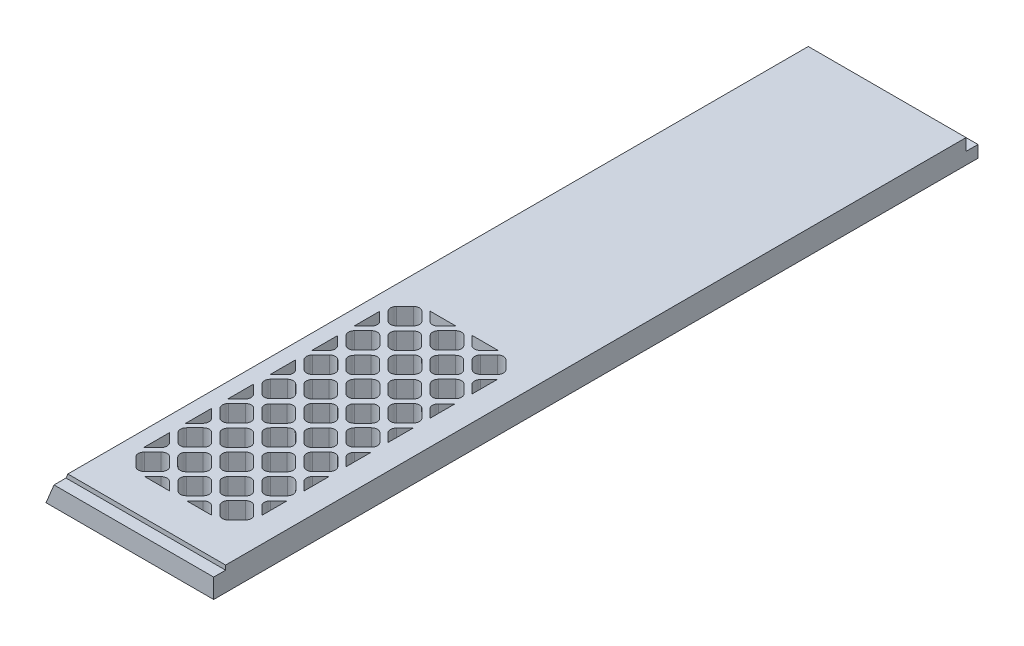
SolidWorks part; units mm, degrees
ref_plane "Front Plane" through (0, 0, 0) normal (0, 0, 1) x (1, 0, 0)
ref_plane "Top Plane" through (0, 0, 0) normal (0, 1, 0) x (1, 0, 0)
ref_plane "Right Plane" through (0, 0, 0) normal (1, 0, 0) x (0, 0, -1)
sketch "Sketch1" plane through (0, 0, 0) normal (0, 0, 1) x (1, 0, 0)
  line L0 (0, 0) -> (5.2605, 12.7)
  line L1 (5.2605, 12.7) -> (89.154, 12.7)
  line L2 (89.154, 12.7) -> (89.154, 0)
  line L3 (89.154, 0) -> (0, 0)
  dimension "D1" = 12.7
  dimension "D2" = 89.154
  dimension "D3" = 67.5
extrude "Boss-Extrude1" add sketch "Sketch1" along normal blind 406.4
sketch "Sketch2" plane through (0, 12.7, 0) normal (0, -1, 0) x (1, 0, 0)
  line L5 (89.154, 406.4) -> (89.154, 0) construction
  line L6 (0, 406.4) -> (89.154, 406.4)
  line L7 (0, 406.4) -> (0, 400.05)
  line L8 (0, 400.05) -> (89.154, 400.05)
  line L9 (89.154, 406.4) -> (89.154, 400.05)
  dimension "D2" = 6.35
extrude "Cut-Extrude1" cut sketch "Sketch2" along normal blind 2.3622
sketch "Sketch3" plane through (0, 0, 0) normal (0, -1, 0) x (1, 0, 0)
  line L90 (0, 203.2) -> (89.154, 203.2) construction
  line L91 (0, 406.4) -> (0, 0) construction
  line L221 (89.154, 406.4) -> (89.154, 0) construction
  line L222 (13.3842, 233.4919) -> (17.8743, 229.0018)
  line L223 (17.8743, 246.8637) -> (13.3842, 242.3736)
  line L235 (13.3842, 255.8439) -> (17.8743, 251.3538)
  line L236 (17.8743, 269.2157) -> (13.3842, 264.7256)
  line L237 (13.3842, 278.1959) -> (17.8743, 273.7058)
  line L238 (17.8743, 291.5677) -> (13.3842, 287.0776)
  line L239 (13.3842, 300.5479) -> (17.8743, 296.0578)
  line L240 (17.8743, 313.9197) -> (13.3842, 309.4296)
  line L241 (13.3842, 322.8999) -> (17.8743, 318.4098)
  line L242 (17.8743, 336.2717) -> (13.3842, 331.7816)
  line L243 (13.3842, 345.2519) -> (17.8743, 340.7618)
  line L244 (17.8743, 358.6237) -> (13.3842, 354.1336)
  line L245 (13.3842, 367.6039) -> (17.8743, 363.1138)
  line L246 (71.4599, 229.0018) -> (75.9093, 233.4512)
  line L247 (49.1079, 229.0018) -> (53.598, 233.4919)
  line L248 (58.0882, 233.4919) -> (62.5783, 229.0018)
  line L249 (26.7559, 229.0018) -> (31.246, 233.4919)
  line L250 (35.7362, 233.4919) -> (40.2263, 229.0018)
  line L251 (71.4599, 251.3538) -> (75.9093, 255.8032)
  line L252 (75.9093, 242.4143) -> (71.4599, 246.8637)
  line L253 (49.1079, 251.3538) -> (53.598, 255.8439)
  line L254 (53.598, 242.3736) -> (49.1079, 246.8637)
  line L255 (62.5783, 246.8637) -> (58.0882, 242.3736)
  line L256 (58.0882, 255.8439) -> (62.5783, 251.3538)
  line L257 (26.7559, 251.3538) -> (31.246, 255.8439)
  line L258 (31.246, 242.3736) -> (26.7559, 246.8637)
  line L259 (40.2263, 246.8637) -> (35.7362, 242.3736)
  line L260 (35.7362, 255.8439) -> (40.2263, 251.3538)
  line L261 (71.4599, 273.7058) -> (75.9093, 278.1552)
  line L262 (75.9093, 264.7663) -> (71.4599, 269.2157)
  line L263 (49.1079, 273.7058) -> (53.598, 278.1959)
  line L264 (53.598, 264.7256) -> (49.1079, 269.2157)
  line L265 (62.5783, 269.2157) -> (58.0882, 264.7256)
  line L266 (58.0882, 278.1959) -> (62.5783, 273.7058)
  line L267 (26.7559, 273.7058) -> (31.246, 278.1959)
  line L268 (31.246, 264.7256) -> (26.7559, 269.2157)
  line L269 (40.2263, 269.2157) -> (35.7362, 264.7256)
  line L270 (35.7362, 278.1959) -> (40.2263, 273.7058)
  line L271 (71.4599, 296.0578) -> (75.9093, 300.5072)
  line L272 (75.9093, 287.1183) -> (71.4599, 291.5677)
  line L273 (49.1079, 296.0578) -> (53.598, 300.5479)
  line L274 (53.598, 287.0776) -> (49.1079, 291.5677)
  line L275 (62.5783, 291.5677) -> (58.0882, 287.0776)
  line L276 (58.0882, 300.5479) -> (62.5783, 296.0578)
  line L277 (26.7559, 296.0578) -> (31.246, 300.5479)
  line L278 (31.246, 287.0776) -> (26.7559, 291.5677)
  line L279 (40.2263, 291.5677) -> (35.7362, 287.0776)
  line L280 (35.7362, 300.5479) -> (40.2263, 296.0578)
  line L281 (71.4599, 318.4098) -> (75.9093, 322.8592)
  line L282 (75.9093, 309.4703) -> (71.4599, 313.9197)
  line L283 (49.1079, 318.4098) -> (53.598, 322.8999)
  line L284 (53.598, 309.4296) -> (49.1079, 313.9197)
  line L285 (62.5783, 313.9197) -> (58.0882, 309.4296)
  line L286 (58.0882, 322.8999) -> (62.5783, 318.4098)
  line L287 (26.7559, 318.4098) -> (31.246, 322.8999)
  line L288 (31.246, 309.4296) -> (26.7559, 313.9197)
  line L289 (40.2263, 313.9197) -> (35.7362, 309.4296)
  line L290 (35.7362, 322.8999) -> (40.2263, 318.4098)
  line L291 (71.4599, 340.7618) -> (75.9093, 345.2112)
  line L292 (75.9093, 331.8223) -> (71.4599, 336.2717)
  line L293 (49.1079, 340.7618) -> (53.598, 345.2519)
  line L294 (53.598, 331.7816) -> (49.1079, 336.2717)
  line L295 (62.5783, 336.2717) -> (58.0882, 331.7816)
  line L296 (58.0882, 345.2519) -> (62.5783, 340.7618)
  line L297 (26.7559, 340.7618) -> (31.246, 345.2519)
  line L298 (31.246, 331.7816) -> (26.7559, 336.2717)
  line L299 (40.2263, 336.2717) -> (35.7362, 331.7816)
  line L300 (35.7362, 345.2519) -> (40.2263, 340.7618)
  line L301 (71.4599, 363.1138) -> (75.9093, 367.5632)
  line L302 (75.9093, 354.1743) -> (71.4599, 358.6237)
  line L303 (49.1079, 363.1138) -> (53.598, 367.6039)
  line L304 (53.598, 354.1336) -> (49.1079, 358.6237)
  line L305 (62.5783, 358.6237) -> (58.0882, 354.1336)
  line L306 (58.0882, 367.6039) -> (62.5783, 363.1138)
  line L307 (26.7559, 363.1138) -> (31.246, 367.6039)
  line L308 (31.246, 354.1336) -> (26.7559, 358.6237)
  line L309 (40.2263, 358.6237) -> (35.7362, 354.1336)
  line L310 (35.7362, 367.6039) -> (40.2263, 363.1138)
  line L311 (75.9093, 376.5263) -> (71.5993, 380.8363)
  line L312 (53.598, 376.4856) -> (49.2473, 380.8363)
  line L313 (62.4389, 380.8363) -> (58.0882, 376.4856)
  line L314 (31.246, 376.4856) -> (26.8953, 380.8363)
  line L315 (40.0869, 380.8363) -> (35.7362, 376.4856)
  line L316 (17.7349, 380.8363) -> (13.3842, 376.4856)
  line L317 (73.6642, 235.4989) -> (69.1741, 231.0088)
  line L318 (69.1741, 244.4792) -> (73.6642, 239.9891)
  line L319 (60.1938, 239.9891) -> (64.6839, 244.4792)
  line L320 (64.6839, 231.0088) -> (60.1938, 235.4989)
  line L321 (51.3122, 235.4989) -> (46.8221, 231.0088)
  line L322 (46.8221, 244.4792) -> (51.3122, 239.9891)
  line L323 (37.8418, 239.9891) -> (42.3319, 244.4792)
  line L324 (42.3319, 231.0088) -> (37.8418, 235.4989)
  line L325 (28.9602, 235.4989) -> (24.4701, 231.0088)
  line L326 (24.4701, 244.4792) -> (28.9602, 239.9891)
  line L327 (15.4898, 239.9891) -> (19.9799, 244.4792)
  line L328 (19.9799, 231.0088) -> (15.4898, 235.4989)
  line L329 (73.6642, 257.8509) -> (69.1741, 253.3608)
  line L330 (69.1741, 266.8312) -> (73.6642, 262.3411)
  line L331 (60.1938, 262.3411) -> (64.6839, 266.8312)
  line L332 (64.6839, 253.3608) -> (60.1938, 257.8509)
  line L333 (51.3122, 257.8509) -> (46.8221, 253.3608)
  line L334 (46.8221, 266.8312) -> (51.3122, 262.3411)
  line L335 (37.8418, 262.3411) -> (42.3319, 266.8312)
  line L336 (42.3319, 253.3608) -> (37.8418, 257.8509)
  line L337 (28.9602, 257.8509) -> (24.4701, 253.3608)
  line L338 (24.4701, 266.8312) -> (28.9602, 262.3411)
  line L339 (15.4898, 262.3411) -> (19.9799, 266.8312)
  line L340 (19.9799, 253.3608) -> (15.4898, 257.8509)
  line L341 (73.6642, 280.2029) -> (69.1741, 275.7128)
  line L342 (69.1741, 289.1832) -> (73.6642, 284.6931)
  line L343 (60.1938, 284.6931) -> (64.6839, 289.1832)
  line L344 (64.6839, 275.7128) -> (60.1938, 280.2029)
  line L345 (51.3122, 280.2029) -> (46.8221, 275.7128)
  line L346 (46.8221, 289.1832) -> (51.3122, 284.6931)
  line L347 (37.8418, 284.6931) -> (42.3319, 289.1832)
  line L348 (42.3319, 275.7128) -> (37.8418, 280.2029)
  line L349 (28.9602, 280.2029) -> (24.4701, 275.7128)
  line L350 (24.4701, 289.1832) -> (28.9602, 284.6931)
  line L351 (15.4898, 284.6931) -> (19.9799, 289.1832)
  line L352 (19.9799, 275.7128) -> (15.4898, 280.2029)
  line L353 (73.6642, 302.5549) -> (69.1741, 298.0648)
  line L354 (69.1741, 311.5352) -> (73.6642, 307.0451)
  line L355 (60.1938, 307.0451) -> (64.6839, 311.5352)
  line L356 (64.6839, 298.0648) -> (60.1938, 302.5549)
  line L357 (51.3122, 302.5549) -> (46.8221, 298.0648)
  line L358 (46.8221, 311.5352) -> (51.3122, 307.0451)
  line L359 (37.8418, 307.0451) -> (42.3319, 311.5352)
  line L360 (42.3319, 298.0648) -> (37.8418, 302.5549)
  line L361 (28.9602, 302.5549) -> (24.4701, 298.0648)
  line L362 (24.4701, 311.5352) -> (28.9602, 307.0451)
  line L363 (15.4898, 307.0451) -> (19.9799, 311.5352)
  line L364 (19.9799, 298.0648) -> (15.4898, 302.5549)
  line L365 (73.6642, 324.9069) -> (69.1741, 320.4168)
  line L366 (69.1741, 333.8872) -> (73.6642, 329.3971)
  line L367 (60.1938, 329.3971) -> (64.6839, 333.8872)
  line L368 (64.6839, 320.4168) -> (60.1938, 324.9069)
  line L369 (51.3122, 324.9069) -> (46.8221, 320.4168)
  line L370 (46.8221, 333.8872) -> (51.3122, 329.3971)
  line L371 (37.8418, 329.3971) -> (42.3319, 333.8872)
  line L372 (42.3319, 320.4168) -> (37.8418, 324.9069)
  line L373 (28.9602, 324.9069) -> (24.4701, 320.4168)
  line L374 (24.4701, 333.8872) -> (28.9602, 329.3971)
  line L375 (15.4898, 329.3971) -> (19.9799, 333.8872)
  line L376 (19.9799, 320.4168) -> (15.4898, 324.9069)
  line L377 (73.6642, 347.2589) -> (69.1741, 342.7688)
  line L378 (69.1741, 356.2392) -> (73.6642, 351.7491)
  line L379 (60.1938, 351.7491) -> (64.6839, 356.2392)
  line L380 (64.6839, 342.7688) -> (60.1938, 347.2589)
  line L381 (51.3122, 347.2589) -> (46.8221, 342.7688)
  line L382 (46.8221, 356.2392) -> (51.3122, 351.7491)
  line L383 (37.8418, 351.7491) -> (42.3319, 356.2392)
  line L384 (42.3319, 342.7688) -> (37.8418, 347.2589)
  line L385 (28.9602, 347.2589) -> (24.4701, 342.7688)
  line L386 (24.4701, 356.2392) -> (28.9602, 351.7491)
  line L387 (15.4898, 351.7491) -> (19.9799, 356.2392)
  line L388 (19.9799, 342.7688) -> (15.4898, 347.2589)
  line L389 (73.6642, 369.6109) -> (69.1741, 365.1208)
  line L390 (69.1741, 378.5912) -> (73.6642, 374.1011)
  line L391 (60.1938, 374.1011) -> (64.6839, 378.5912)
  line L392 (64.6839, 365.1208) -> (60.1938, 369.6109)
  line L393 (51.3122, 369.6109) -> (46.8221, 365.1208)
  line L394 (46.8221, 378.5912) -> (51.3122, 374.1011)
  line L395 (37.8418, 374.1011) -> (42.3319, 378.5912)
  line L396 (42.3319, 365.1208) -> (37.8418, 369.6109)
  line L397 (19.9799, 365.1208) -> (15.4898, 369.6109)
  line L398 (28.9602, 369.6109) -> (24.4701, 365.1208)
  line L399 (24.4701, 378.5912) -> (28.9602, 374.1011)
  line L400 (75.9093, 380.8363) -> (75.9093, 228.7637)
  line L401 (13.2447, 228.7637) -> (75.9093, 228.7637)
  line L402 (13.2447, 380.8363) -> (13.2447, 228.7637)
  line L403 (13.2447, 380.8363) -> (75.9093, 380.8363)
  line L404 (15.4898, 374.1011) -> (19.9799, 378.5912)
  arc A212 (18.0894, 228.7637) -> (17.8743, 229.0018) centre (15.6292, 226.7568) ccw
  arc A224 (13.2447, 233.6232) -> (13.3842, 233.4919) centre (11.1391, 231.2469) cw
  arc A225 (13.3842, 242.3736) -> (13.2447, 242.2423) centre (11.1391, 244.6186) cw
  arc A226 (17.8743, 246.8637) -> (17.8743, 251.3538) centre (15.6292, 249.1088) ccw
  arc A227 (13.2447, 255.9752) -> (13.3842, 255.8439) centre (11.1391, 253.5989) cw
  arc A228 (13.3842, 264.7256) -> (13.2447, 264.5943) centre (11.1391, 266.9706) cw
  arc A229 (17.8743, 269.2157) -> (17.8743, 273.7058) centre (15.6292, 271.4608) ccw
  arc A230 (13.2447, 278.3272) -> (13.3842, 278.1959) centre (11.1391, 275.9509) cw
  arc A231 (13.3842, 287.0776) -> (13.2447, 286.9463) centre (11.1391, 289.3226) cw
  arc A232 (17.8743, 291.5677) -> (17.8743, 296.0578) centre (15.6292, 293.8128) ccw
  arc A233 (13.2447, 300.6792) -> (13.3842, 300.5479) centre (11.1391, 298.3029) cw
  arc A234 (13.3842, 309.4296) -> (13.2447, 309.2983) centre (11.1391, 311.6746) cw
  arc A235 (17.8743, 313.9197) -> (17.8743, 318.4098) centre (15.6292, 316.1648) ccw
  arc A236 (13.2447, 323.0312) -> (13.3842, 322.8999) centre (11.1391, 320.6549) cw
  arc A237 (13.3842, 331.7816) -> (13.2447, 331.6503) centre (11.1391, 334.0266) cw
  arc A238 (17.8743, 336.2717) -> (17.8743, 340.7618) centre (15.6292, 338.5168) ccw
  arc A239 (13.2447, 345.3832) -> (13.3842, 345.2519) centre (11.1391, 343.0069) cw
  arc A240 (13.3842, 354.1336) -> (13.2447, 354.0023) centre (11.1391, 356.3786) cw
  arc A241 (17.8743, 358.6237) -> (17.8743, 363.1138) centre (15.6292, 360.8688) ccw
  arc A242 (13.2447, 367.7352) -> (13.3842, 367.6039) centre (11.1391, 365.3589) cw
  arc A243 (71.2448, 228.7637) -> (71.4599, 229.0018) centre (73.705, 226.7568) cw
  arc A244 (48.8928, 228.7637) -> (49.1079, 229.0018) centre (51.353, 226.7568) cw
  arc A245 (62.7934, 228.7637) -> (62.5783, 229.0018) centre (60.3332, 226.7568) ccw
  arc A246 (53.598, 233.4919) -> (58.0882, 233.4919) centre (55.8431, 231.2469) cw
  arc A247 (26.5408, 228.7637) -> (26.7559, 229.0018) centre (29.001, 226.7568) cw
  arc A248 (40.4414, 228.7637) -> (40.2263, 229.0018) centre (37.9812, 226.7568) ccw
  arc A249 (31.246, 233.4919) -> (35.7362, 233.4919) centre (33.4911, 231.2469) cw
  arc A250 (71.4599, 246.8637) -> (71.4599, 251.3538) centre (73.705, 249.1088) cw
  arc A251 (49.1079, 246.8637) -> (49.1079, 251.3538) centre (51.353, 249.1088) cw
  arc A252 (58.0882, 242.3736) -> (53.598, 242.3736) centre (55.8431, 244.6186) cw
  arc A253 (62.5783, 246.8637) -> (62.5783, 251.3538) centre (60.3332, 249.1088) ccw
  arc A254 (53.598, 255.8439) -> (58.0882, 255.8439) centre (55.8431, 253.5989) cw
  arc A255 (26.7559, 246.8637) -> (26.7559, 251.3538) centre (29.001, 249.1088) cw
  arc A256 (35.7362, 242.3736) -> (31.246, 242.3736) centre (33.4911, 244.6186) cw
  arc A257 (40.2263, 246.8637) -> (40.2263, 251.3538) centre (37.9812, 249.1088) ccw
  arc A258 (31.246, 255.8439) -> (35.7362, 255.8439) centre (33.4911, 253.5989) cw
  arc A259 (71.4599, 269.2157) -> (71.4599, 273.7058) centre (73.705, 271.4608) cw
  arc A260 (49.1079, 269.2157) -> (49.1079, 273.7058) centre (51.353, 271.4608) cw
  arc A261 (58.0882, 264.7256) -> (53.598, 264.7256) centre (55.8431, 266.9706) cw
  arc A262 (62.5783, 269.2157) -> (62.5783, 273.7058) centre (60.3332, 271.4608) ccw
  arc A263 (53.598, 278.1959) -> (58.0882, 278.1959) centre (55.8431, 275.9509) cw
  arc A264 (26.7559, 269.2157) -> (26.7559, 273.7058) centre (29.001, 271.4608) cw
  arc A265 (35.7362, 264.7256) -> (31.246, 264.7256) centre (33.4911, 266.9706) cw
  arc A266 (40.2263, 269.2157) -> (40.2263, 273.7058) centre (37.9812, 271.4608) ccw
  arc A267 (31.246, 278.1959) -> (35.7362, 278.1959) centre (33.4911, 275.9509) cw
  arc A268 (71.4599, 291.5677) -> (71.4599, 296.0578) centre (73.705, 293.8128) cw
  arc A269 (49.1079, 291.5677) -> (49.1079, 296.0578) centre (51.353, 293.8128) cw
  arc A270 (58.0882, 287.0776) -> (53.598, 287.0776) centre (55.8431, 289.3226) cw
  arc A271 (62.5783, 291.5677) -> (62.5783, 296.0578) centre (60.3332, 293.8128) ccw
  arc A272 (53.598, 300.5479) -> (58.0882, 300.5479) centre (55.8431, 298.3029) cw
  arc A273 (26.7559, 291.5677) -> (26.7559, 296.0578) centre (29.001, 293.8128) cw
  arc A274 (35.7362, 287.0776) -> (31.246, 287.0776) centre (33.4911, 289.3226) cw
  arc A275 (40.2263, 291.5677) -> (40.2263, 296.0578) centre (37.9812, 293.8128) ccw
  arc A276 (31.246, 300.5479) -> (35.7362, 300.5479) centre (33.4911, 298.3029) cw
  arc A277 (71.4599, 313.9197) -> (71.4599, 318.4098) centre (73.705, 316.1648) cw
  arc A278 (49.1079, 313.9197) -> (49.1079, 318.4098) centre (51.353, 316.1648) cw
  arc A279 (58.0882, 309.4296) -> (53.598, 309.4296) centre (55.8431, 311.6746) cw
  arc A280 (62.5783, 313.9197) -> (62.5783, 318.4098) centre (60.3332, 316.1648) ccw
  arc A281 (53.598, 322.8999) -> (58.0882, 322.8999) centre (55.8431, 320.6549) cw
  arc A282 (26.7559, 313.9197) -> (26.7559, 318.4098) centre (29.001, 316.1648) cw
  arc A283 (35.7362, 309.4296) -> (31.246, 309.4296) centre (33.4911, 311.6746) cw
  arc A284 (40.2263, 313.9197) -> (40.2263, 318.4098) centre (37.9812, 316.1648) ccw
  arc A285 (31.246, 322.8999) -> (35.7362, 322.8999) centre (33.4911, 320.6549) cw
  arc A286 (71.4599, 336.2717) -> (71.4599, 340.7618) centre (73.705, 338.5168) cw
  arc A287 (49.1079, 336.2717) -> (49.1079, 340.7618) centre (51.353, 338.5168) cw
  arc A288 (58.0882, 331.7816) -> (53.598, 331.7816) centre (55.8431, 334.0266) cw
  arc A289 (62.5783, 336.2717) -> (62.5783, 340.7618) centre (60.3332, 338.5168) ccw
  arc A290 (53.598, 345.2519) -> (58.0882, 345.2519) centre (55.8431, 343.0069) cw
  arc A291 (26.7559, 336.2717) -> (26.7559, 340.7618) centre (29.001, 338.5168) cw
  arc A292 (35.7362, 331.7816) -> (31.246, 331.7816) centre (33.4911, 334.0266) cw
  arc A293 (40.2263, 336.2717) -> (40.2263, 340.7618) centre (37.9812, 338.5168) ccw
  arc A294 (31.246, 345.2519) -> (35.7362, 345.2519) centre (33.4911, 343.0069) cw
  arc A295 (71.4599, 358.6237) -> (71.4599, 363.1138) centre (73.705, 360.8688) cw
  arc A296 (49.1079, 358.6237) -> (49.1079, 363.1138) centre (51.353, 360.8688) cw
  arc A297 (58.0882, 354.1336) -> (53.598, 354.1336) centre (55.8431, 356.3786) cw
  arc A298 (62.5783, 358.6237) -> (62.5783, 363.1138) centre (60.3332, 360.8688) ccw
  arc A299 (53.598, 367.6039) -> (58.0882, 367.6039) centre (55.8431, 365.3589) cw
  arc A300 (26.7559, 358.6237) -> (26.7559, 363.1138) centre (29.001, 360.8688) cw
  arc A301 (35.7362, 354.1336) -> (31.246, 354.1336) centre (33.4911, 356.3786) cw
  arc A302 (40.2263, 358.6237) -> (40.2263, 363.1138) centre (37.9812, 360.8688) ccw
  arc A303 (31.246, 367.6039) -> (35.7362, 367.6039) centre (33.4911, 365.3589) cw
  arc A304 (58.0882, 376.4856) -> (53.598, 376.4856) centre (55.8431, 378.7306) cw
  arc A305 (35.7362, 376.4856) -> (31.246, 376.4856) centre (33.4911, 378.7306) cw
  arc A306 (13.3842, 376.4856) -> (13.2447, 376.3543) centre (11.1391, 378.7306) cw
  arc A307 (69.1741, 231.0088) -> (64.6839, 231.0088) centre (66.929, 233.2539) cw
  arc A308 (73.6642, 239.9891) -> (73.6642, 235.4989) centre (71.4191, 237.744) cw
  arc A309 (64.6839, 244.4792) -> (69.1741, 244.4792) centre (66.929, 242.2341) cw
  arc A310 (60.1938, 239.9891) -> (60.1938, 235.4989) centre (62.4389, 237.744) ccw
  arc A311 (46.8221, 231.0088) -> (42.3319, 231.0088) centre (44.577, 233.2539) cw
  arc A312 (51.3122, 239.9891) -> (51.3122, 235.4989) centre (49.0671, 237.744) cw
  arc A313 (42.3319, 244.4792) -> (46.8221, 244.4792) centre (44.577, 242.2341) cw
  arc A314 (37.8418, 239.9891) -> (37.8418, 235.4989) centre (40.0869, 237.744) ccw
  arc A315 (28.9602, 239.9891) -> (28.9602, 235.4989) centre (26.7151, 237.744) cw
  arc A316 (19.9799, 244.4792) -> (24.4701, 244.4792) centre (22.225, 242.2341) cw
  arc A317 (24.4701, 231.0088) -> (19.9799, 231.0088) centre (22.225, 233.2539) cw
  arc A318 (15.4898, 239.9891) -> (15.4898, 235.4989) centre (17.7349, 237.744) ccw
  arc A319 (69.1741, 253.3608) -> (64.6839, 253.3608) centre (66.929, 255.6059) cw
  arc A320 (73.6642, 262.3411) -> (73.6642, 257.8509) centre (71.4191, 260.096) cw
  arc A321 (64.6839, 266.8312) -> (69.1741, 266.8312) centre (66.929, 264.5861) cw
  arc A322 (60.1938, 262.3411) -> (60.1938, 257.8509) centre (62.4389, 260.096) ccw
  arc A323 (46.8221, 253.3608) -> (42.3319, 253.3608) centre (44.577, 255.6059) cw
  arc A324 (51.3122, 262.3411) -> (51.3122, 257.8509) centre (49.0671, 260.096) cw
  arc A325 (42.3319, 266.8312) -> (46.8221, 266.8312) centre (44.577, 264.5861) cw
  arc A326 (37.8418, 262.3411) -> (37.8418, 257.8509) centre (40.0869, 260.096) ccw
  arc A327 (28.9602, 262.3411) -> (28.9602, 257.8509) centre (26.7151, 260.096) cw
  arc A328 (19.9799, 266.8312) -> (24.4701, 266.8312) centre (22.225, 264.5861) cw
  arc A329 (24.4701, 253.3608) -> (19.9799, 253.3608) centre (22.225, 255.6059) cw
  arc A330 (15.4898, 262.3411) -> (15.4898, 257.8509) centre (17.7349, 260.096) ccw
  arc A331 (69.1741, 275.7128) -> (64.6839, 275.7128) centre (66.929, 277.9579) cw
  arc A332 (73.6642, 284.6931) -> (73.6642, 280.2029) centre (71.4191, 282.448) cw
  arc A333 (64.6839, 289.1832) -> (69.1741, 289.1832) centre (66.929, 286.9381) cw
  arc A334 (60.1938, 284.6931) -> (60.1938, 280.2029) centre (62.4389, 282.448) ccw
  arc A335 (46.8221, 275.7128) -> (42.3319, 275.7128) centre (44.577, 277.9579) cw
  arc A336 (51.3122, 284.6931) -> (51.3122, 280.2029) centre (49.0671, 282.448) cw
  arc A337 (42.3319, 289.1832) -> (46.8221, 289.1832) centre (44.577, 286.9381) cw
  arc A338 (37.8418, 284.6931) -> (37.8418, 280.2029) centre (40.0869, 282.448) ccw
  arc A339 (28.9602, 284.6931) -> (28.9602, 280.2029) centre (26.7151, 282.448) cw
  arc A340 (19.9799, 289.1832) -> (24.4701, 289.1832) centre (22.225, 286.9381) cw
  arc A341 (24.4701, 275.7128) -> (19.9799, 275.7128) centre (22.225, 277.9579) cw
  arc A342 (15.4898, 284.6931) -> (15.4898, 280.2029) centre (17.7349, 282.448) ccw
  arc A343 (69.1741, 298.0648) -> (64.6839, 298.0648) centre (66.929, 300.3099) cw
  arc A344 (73.6642, 307.0451) -> (73.6642, 302.5549) centre (71.4191, 304.8) cw
  arc A345 (64.6839, 311.5352) -> (69.1741, 311.5352) centre (66.929, 309.2901) cw
  arc A346 (60.1938, 307.0451) -> (60.1938, 302.5549) centre (62.4389, 304.8) ccw
  arc A347 (46.8221, 298.0648) -> (42.3319, 298.0648) centre (44.577, 300.3099) cw
  arc A348 (51.3122, 307.0451) -> (51.3122, 302.5549) centre (49.0671, 304.8) cw
  arc A349 (42.3319, 311.5352) -> (46.8221, 311.5352) centre (44.577, 309.2901) cw
  arc A350 (37.8418, 307.0451) -> (37.8418, 302.5549) centre (40.0869, 304.8) ccw
  arc A351 (28.9602, 307.0451) -> (28.9602, 302.5549) centre (26.7151, 304.8) cw
  arc A352 (19.9799, 311.5352) -> (24.4701, 311.5352) centre (22.225, 309.2901) cw
  arc A353 (24.4701, 298.0648) -> (19.9799, 298.0648) centre (22.225, 300.3099) cw
  arc A354 (15.4898, 307.0451) -> (15.4898, 302.5549) centre (17.7349, 304.8) ccw
  arc A355 (69.1741, 320.4168) -> (64.6839, 320.4168) centre (66.929, 322.6619) cw
  arc A356 (73.6642, 329.3971) -> (73.6642, 324.9069) centre (71.4191, 327.152) cw
  arc A357 (64.6839, 333.8872) -> (69.1741, 333.8872) centre (66.929, 331.6421) cw
  arc A358 (60.1938, 329.3971) -> (60.1938, 324.9069) centre (62.4389, 327.152) ccw
  arc A359 (46.8221, 320.4168) -> (42.3319, 320.4168) centre (44.577, 322.6619) cw
  arc A360 (51.3122, 329.3971) -> (51.3122, 324.9069) centre (49.0671, 327.152) cw
  arc A361 (42.3319, 333.8872) -> (46.8221, 333.8872) centre (44.577, 331.6421) cw
  arc A362 (37.8418, 329.3971) -> (37.8418, 324.9069) centre (40.0869, 327.152) ccw
  arc A363 (28.9602, 329.3971) -> (28.9602, 324.9069) centre (26.7151, 327.152) cw
  arc A364 (19.9799, 333.8872) -> (24.4701, 333.8872) centre (22.225, 331.6421) cw
  arc A365 (24.4701, 320.4168) -> (19.9799, 320.4168) centre (22.225, 322.6619) cw
  arc A366 (15.4898, 329.3971) -> (15.4898, 324.9069) centre (17.7349, 327.152) ccw
  arc A367 (69.1741, 342.7688) -> (64.6839, 342.7688) centre (66.929, 345.0139) cw
  arc A368 (73.6642, 351.7491) -> (73.6642, 347.2589) centre (71.4191, 349.504) cw
  arc A369 (64.6839, 356.2392) -> (69.1741, 356.2392) centre (66.929, 353.9941) cw
  arc A370 (60.1938, 351.7491) -> (60.1938, 347.2589) centre (62.4389, 349.504) ccw
  arc A371 (46.8221, 342.7688) -> (42.3319, 342.7688) centre (44.577, 345.0139) cw
  arc A372 (51.3122, 351.7491) -> (51.3122, 347.2589) centre (49.0671, 349.504) cw
  arc A373 (42.3319, 356.2392) -> (46.8221, 356.2392) centre (44.577, 353.9941) cw
  arc A374 (37.8418, 351.7491) -> (37.8418, 347.2589) centre (40.0869, 349.504) ccw
  arc A375 (28.9602, 351.7491) -> (28.9602, 347.2589) centre (26.7151, 349.504) cw
  arc A376 (19.9799, 356.2392) -> (24.4701, 356.2392) centre (22.225, 353.9941) cw
  arc A377 (24.4701, 342.7688) -> (19.9799, 342.7688) centre (22.225, 345.0139) cw
  arc A378 (15.4898, 351.7491) -> (15.4898, 347.2589) centre (17.7349, 349.504) ccw
  arc A379 (73.6642, 374.1011) -> (73.6642, 369.6109) centre (71.4191, 371.856) cw
  arc A380 (64.6839, 378.5912) -> (69.1741, 378.5912) centre (66.929, 376.3461) cw
  arc A381 (69.1741, 365.1208) -> (64.6839, 365.1208) centre (66.929, 367.3659) cw
  arc A382 (60.1938, 374.1011) -> (60.1938, 369.6109) centre (62.4389, 371.856) ccw
  arc A383 (51.3122, 374.1011) -> (51.3122, 369.6109) centre (49.0671, 371.856) cw
  arc A384 (42.3319, 378.5912) -> (46.8221, 378.5912) centre (44.577, 376.3461) cw
  arc A385 (46.8221, 365.1208) -> (42.3319, 365.1208) centre (44.577, 367.3659) cw
  arc A386 (37.8418, 374.1011) -> (37.8418, 369.6109) centre (40.0869, 371.856) ccw
  arc A387 (15.4898, 374.1011) -> (15.4898, 369.6109) centre (17.7349, 371.856) ccw
  arc A388 (19.9799, 378.5912) -> (24.4701, 378.5912) centre (22.225, 376.3461) cw
  arc A389 (24.4701, 365.1208) -> (19.9799, 365.1208) centre (22.225, 367.3659) cw
  arc A390 (28.9602, 374.1011) -> (28.9602, 369.6109) centre (26.7151, 371.856) cw
  point P1134 (2.1589, 383.2208)
  point P1135 (11.1391, 392.201)
  point P1136 (20.1194, 383.2208)
  point P1137 (13.2447, 371.856)
  point P1138 (22.225, 380.8363)
  point P1139 (31.2053, 371.856)
extrude "Cut-Extrude2" cut sketch "Sketch3" against normal through all contours A390 L399 A388 L404 A387 L397 A389 L398 | L395 A386 L396 A385 L393 A383 L394 A384 | L391 A382 L392 A381 L389 A379 L390 A380 | A299 L303 A296 L304 A297 L305 A298 L306 | A303 L307 A300 L308 A301 L309 A302 L310 | L387 A378 L388 A377 L385 A375 L386 A376 | L383 A374 L384 A371 L381 A372 L382 A373 | L379 A370 L380 A367 L377 A368 L378 A369 | A290 L293 A287 L294 A288 L295 A289 L296 | A294 L297 A291 L298 A292 L299 A293 L300 | L375 A366 L376 A365 L373 A363 L374 A364 | L371 A362 L372 A359 L369 A360 L370 A361 | L367 A358 L368 A355 L365 A356 L366 A357 | A285 L287 A282 L288 A283 L289 A284 L290 | A281 L283 A278 L284 A279 L285 A280 L286 | L363 A354 L364 A353 L361 A351 L362 A352 | L359 A350 L360 A347 L357 A348 L358 A349 | L355 A346 L356 A343 L353 A344 L354 A345 | A272 L273 A269 L274 A270 L275 A271 L276 | A276 L277 A273 L278 A274 L279 A275 L280 | L351 A342 L352 A341 L349 A339 L350 A340 | L339 A330 L340 A329 L337 A327 L338 A328 | L327 A318 L328 A317 L325 A315 L326 A316 | A258 L257 A255 L258 A256 L259 A257 L260 | A267 L267 A264 L268 A265 L269 A266 L270 | L347 A338 L348 A335 L345 A336 L346 A337 | L335 A326 L336 A323 L333 A324 L334 A325 | L323 A314 L324 A311 L321 A312 L322 A313 | A263 L263 A260 L264 A261 L265 A262 L266 | L343 A334 L344 A331 L341 A332 L342 A333 | L331 A322 L332 A319 L329 A320 L330 A321 | A254 L253 A251 L254 A252 L255 A253 L256 | L319 A310 L320 A307 L317 A308 L318 A309 | A242 L402 A240 L244 A241 L245 | A239 L402 A237 L242 A238 L243 | A236 L402 A234 L240 A235 L241 | A305 L315 L403 L314 | A304 L313 L403 L312 | A295 L302 L400 L301 | A286 L292 L400 L291 | A277 L282 L400 L281 | A268 L272 L400 L271 | A233 L402 A231 L238 A232 L239 | A259 L262 L400 L261 | A250 L252 L400 L251 | A246 L247 A244 L401 A245 L248 | A249 L249 A247 L401 A248 L250 | A227 L402 A225 L223 A226 L235 | A230 L402 A228 L236 A229 L237 region at (15.3646, 0, 249.1088) region at (33.4911, 0, 230.9186) region at (15.3646, 0, 271.4608) region at (55.8431, 0, 230.9186) region at (15.3646, 0, 293.8128) region at (15.3646, 0, 316.1648) region at (73.8533, 0, 249.1088) region at (15.3646, 0, 338.5168) region at (73.8533, 0, 271.4608) region at (15.3646, 0, 360.8688) region at (73.8533, 0, 293.8128) region at (73.8533, 0, 316.1648) region at (33.4911, 0, 378.8153) region at (73.8533, 0, 338.5168) region at (55.8431, 0, 378.8153) region at (73.8533, 0, 360.8688) region at (55.8431, 0, 249.1088) region at (33.4911, 0, 249.1088) region at (55.8431, 0, 271.4608) region at (33.4911, 0, 271.4608) region at (55.8431, 0, 293.8128) region at (33.4911, 0, 293.8128) region at (55.8431, 0, 316.1648) region at (33.4911, 0, 316.1648) region at (55.8431, 0, 338.5168) region at (33.4911, 0, 338.5168) region at (55.8431, 0, 360.8688) region at (33.4911, 0, 360.8688) region at (66.929, 0, 237.744) region at (44.577, 0, 237.744) region at (22.225, 0, 237.744) region at (66.929, 0, 260.096) region at (44.577, 0, 260.096) region at (22.225, 0, 260.096) region at (66.929, 0, 282.448) region at (44.577, 0, 282.448) region at (22.225, 0, 282.448) region at (66.929, 0, 304.8) region at (44.577, 0, 304.8) region at (22.225, 0, 304.8) region at (66.929, 0, 327.152) region at (44.577, 0, 327.152) region at (22.225, 0, 327.152) region at (66.929, 0, 349.504) region at (44.577, 0, 349.504) region at (22.225, 0, 349.504) region at (66.929, 0, 371.856) region at (44.577, 0, 371.856) region at (22.225, 0, 371.856)
sketch "Sketch4" plane through (0, 12.7, 0) normal (0, 1, 0) x (1, 0, 0)
  line L1 (89.154, 0) -> (-9.1024, 0)
  line L2 (89.154, 0) -> (89.154, -6.35)
  line L3 (89.154, -6.35) -> (-9.1024, -6.35)
  line L4 (-9.1024, 0) -> (-9.1024, -6.35)
  dimension "D1" = 6.35
extrude "Cut-Extrude3" cut sketch "Sketch4" against normal blind 6.35
